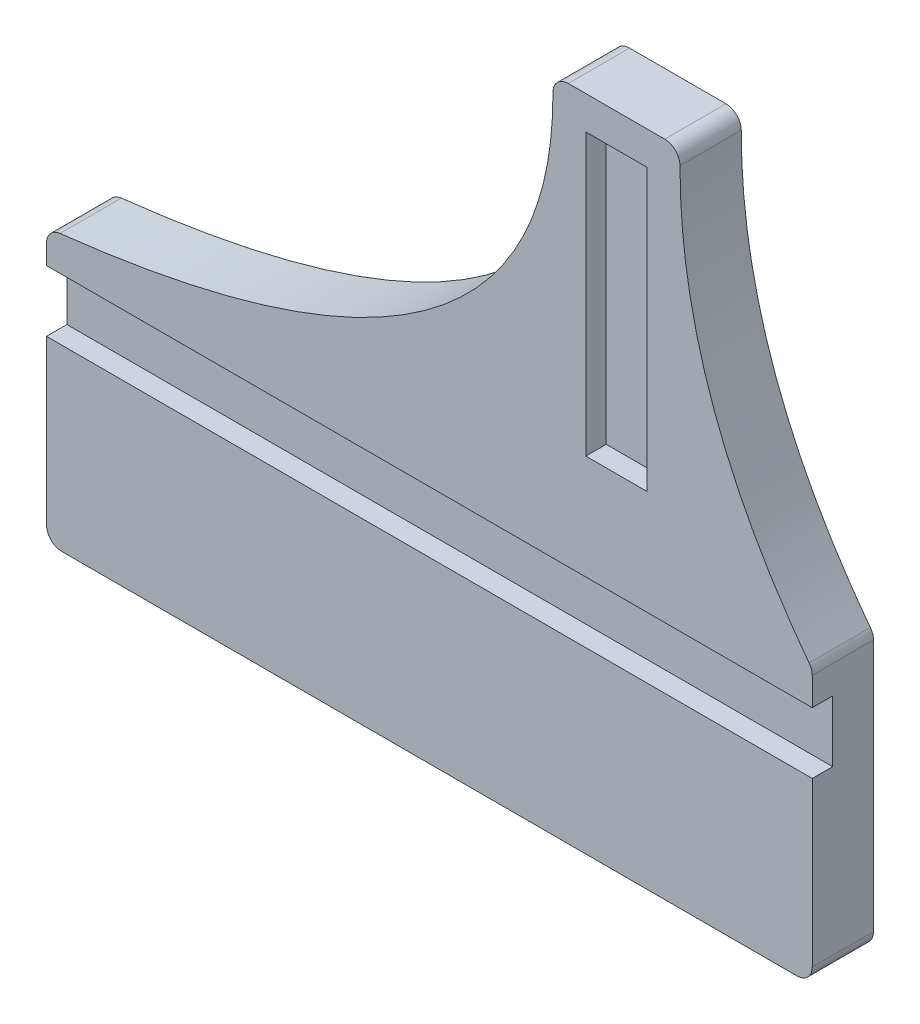
SolidWorks part; units mm, degrees
ref_plane "Ebene vorne" through (0, 0, 0) normal (0, 0, 1) x (1, 0, 0)
ref_plane "Ebene oben" through (0, 0, 0) normal (0, 1, 0) x (1, 0, 0)
ref_plane "Ebene rechts" through (0, 0, 0) normal (1, 0, 0) x (0, 0, -1)
sketch "Skizze1" plane through (0, 0, 0) normal (0, 0, 1) x (1, 0, 0)
  line L0 (24.14, 88) -> (49.14, 88)
  line L3 (75, 12.5) -> (75, -41)
  line L4 (75, -41) -> (-75, -41)
  line L9 (-75, -41) -> (-75, 12.5)
  line L13 (30.64, 81.5) -> (42.64, 81.5)
  line L14 (30.64, 81.5) -> (30.64, 26.5)
  line L15 (30.64, 26.5) -> (42.64, 26.5)
  line L16 (42.64, 81.5) -> (42.64, 26.5)
  line L17 (30.64, 81.5) -> (42.64, 26.5) construction
  line L18 (30.64, 26.5) -> (42.64, 81.5) construction
  line L19 (-75, 6) -> (75, 6)
  line L20 (-75, 6) -> (-75, -6)
  line L21 (-75, -6) -> (75, -6)
  line L22 (75, 6) -> (75, -6)
  line L23 (-75, 6) -> (75, -6) construction
  line L24 (-75, -6) -> (75, 6) construction
  line L26 (-75, 12.5) -> (75, 12.5) construction
  line L27 (24.14, 81.5) -> (49.14, 81.5) construction
  spline S0 degree 2 poles (24.14, 88) (26.8075, 22.9626) (-75, 12.5) knots 0 0 0 1 1 1
  spline S1 degree 2 poles (49.14, 88) (47.9994, 47.6999) (75, 12.5) knots 0 0 0 1 1 1
  point P2 (0, -41)
  point P3 (40.64, 98.3862)
  point P7 (0, 0)
  point P8 (0, 0)
  point P9 (0, 0)
  point P12 (0, 0)
  point P13 (36.64, 88)
  point P16 (36.64, 54)
  point P23 (0, 0)
  dimension "D2" = 25
  dimension "D3" = 150
  dimension "D4" = 35
  dimension "D5" = 36.64
  dimension "D6" = 6.5
  dimension "D7" = 69
  dimension "D8" = 6.5
  dimension "D9" = 12
  dimension "D10" = 55
  dimension "D11" = 12
extrude "Aufsatz-Linear austragen1" add sketch "Skizze1" against normal blind 12 contours S1 L0 S0 L9 L19 L3 L13 L16 L15 L14 | L16 L13 L14 L15 | L9 L21 L3 L19 | L21 L9 L4 L3 region at (18.2385, 29.5651, 0) region at (0, 0, 0) region at (0, -23.5, 0) region at (36.64, 54, 0)
extrude "Schnitt-Linear austragen2" cut sketch "Skizze1<4>" against normal blind 4 contours L16 L13 L14 L15 | L20 L19 L22 L21 region at (36.64, 54, 0)
sketch "Skizze1<4>" plane through (0, 0, 0) normal (0, 0, 1) x (1, 0, 0) same geometry as "Skizze1"
fillet "Verrundung1" radius 3 6 edges at (75, -41, -6) (75, 12.5, -6) (49.14, 88, -6) (-75, -41, -6) (-75, 12.5, -6) (24.14, 88, -6)
